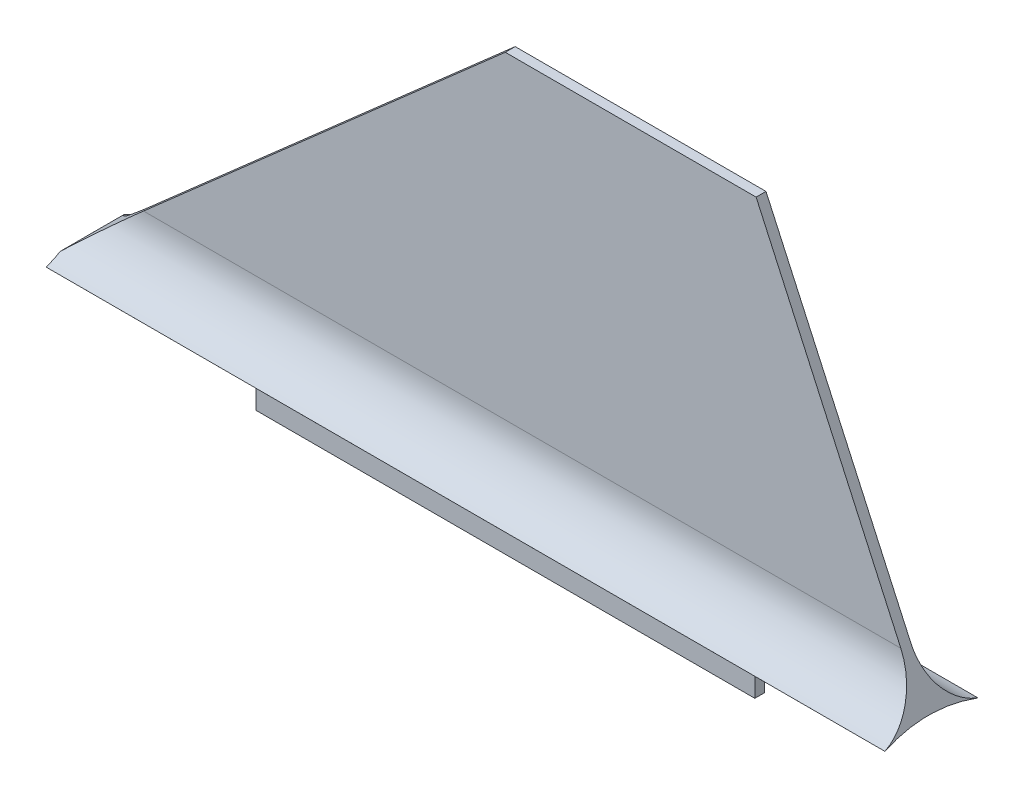
SolidWorks part; units mm, degrees
material "A-Glass Fiber"
ref_plane "Front Plane" through (0, 0, 0) normal (0, 0, 1) x (1, 0, 0)
ref_plane "Top Plane" through (0, 0, 0) normal (0, 1, 0) x (1, 0, 0)
ref_plane "Right Plane" through (0, 0, 0) normal (1, 0, 0) x (0, 0, -1)
sketch "Sketch1" plane through (0, 0, 0) normal (0, 0, 1) x (1, 0, 0)
  line L0 (0, 0) -> (127, 111.76)
  line L1 (127, 111.76) -> (203.2, 111.76)
  line L2 (203.2, 111.76) -> (254, 0)
  line L3 (254, 0) -> (202.8063, 0)
  line L4 (202.8063, 0) -> (202.8063, -20.32)
  line L5 (202.8063, -20.32) -> (51.1937, -20.32)
  line L6 (51.1937, -20.32) -> (51.1937, 0)
  line L7 (51.1937, 0) -> (0, 0)
  line L8 (0, 0) -> (0, 111.76) construction
  line L9 (0, 111.76) -> (127, 111.76) construction
  dimension "D1" = 20.32
  dimension "D2" = 151.6126
  dimension "D3" = 254
  dimension "D4" = 76.2
  dimension "D5" = 127
  dimension "D6" = 111.76
extrude "Boss-Extrude1" add sketch "Sketch1" along normal blind 2.9972
sketch "Sketch2" plane through (0, 0, 0) normal (1, 0, 0) x (0, 0, -1)
  line L1 (-2.9972, 0) -> (0, 0) construction
  arc A0 (12.7, -2.0025) -> (-15.5453, -1.9585) centre (-1.4986, -50.7779) ccw
  point P8 (-1.4986, 0)
  dimension "D1" = 50.8
  dimension "D3" = 12.7
  dimension "D4" = 12.7
extrude "Extrude-Thin1" add sketch "Sketch2" along normal up to surface (254.9102 mm away) thin up to face at (228.6, 55.88, 1.4986) thin type one direction reverse wall 0.0025
fillet "Fillet1" radius 17.78 2 edges at (127, 0, 0) (127, 0, 2.9972)
